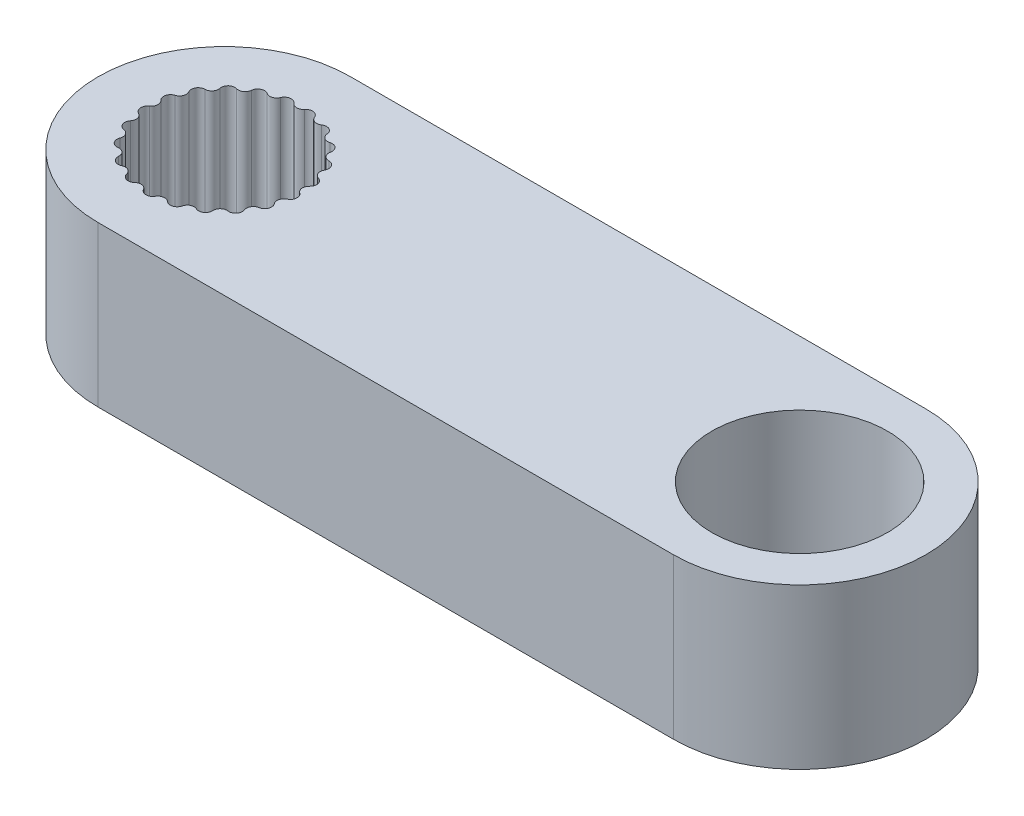
SolidWorks part; units mm, degrees
ref_plane "Front Plane" through (0, 0, 0) normal (0, 0, 1) x (1, 0, 0)
ref_plane "Top Plane" through (0, 0, 0) normal (0, 1, 0) x (1, 0, 0)
ref_plane "Right Plane" through (0, 0, 0) normal (1, 0, 0) x (0, 0, -1)
sketch "Sketch1" plane through (0, 0, 0) normal (0, 1, 0) x (1, 0, 0)
  line L0 (0, 0) -> (0, 4.4464) construction
  line L1 (0, 0) -> (0.6627, 4.3968) construction
  line L2 (0, 0) -> (1.3106, 4.2489) construction
  line L3 (0, 0) -> (1.9292, 4.0061) construction
  line L4 (0, 0) -> (2.5048, 3.6738) construction
  line L5 (0, 0) -> (3.0243, 3.2595) construction
  line L6 (0, 0) -> (3.4764, 2.7723) construction
  line L7 (0, 0) -> (3.8507, 2.2232) construction
  line L8 (0, 0) -> (4.1391, 1.6245) construction
  line L9 (0, 0) -> (4.3349, 0.9894) construction
  line L10 (0, 0) -> (4.434, 0.3323) construction
  line L11 (0, 0) -> (4.434, -0.3323) construction
  line L12 (0, 0) -> (4.3349, -0.9894) construction
  line L13 (0, 0) -> (4.1391, -1.6245) construction
  line L14 (0, 0) -> (3.8507, -2.2232) construction
  line L15 (0, 0) -> (3.4764, -2.7723) construction
  line L16 (0, 0) -> (3.0243, -3.2595) construction
  line L17 (0, 0) -> (2.5048, -3.6738) construction
  line L18 (0, 0) -> (1.9292, -4.0061) construction
  line L19 (0, 0) -> (1.3106, -4.2489) construction
  line L20 (0, 0) -> (0.6627, -4.3968) construction
  line L21 (0, 0) -> (0, -4.4464) construction
  line L22 (0, 0) -> (-0.6627, -4.3968) construction
  line L23 (0, 0) -> (-1.3106, -4.2489) construction
  line L24 (0, 0) -> (-1.9292, -4.0061) construction
  line L25 (0, 0) -> (-2.5048, -3.6738) construction
  line L26 (0, 0) -> (-3.0243, -3.2595) construction
  line L27 (0, 0) -> (-3.4764, -2.7723) construction
  line L28 (0, 0) -> (-3.8507, -2.2232) construction
  line L29 (0, 0) -> (-4.1391, -1.6245) construction
  line L30 (0, 0) -> (-4.3349, -0.9894) construction
  line L31 (0, 0) -> (-4.434, -0.3323) construction
  line L32 (0, 0) -> (-4.434, 0.3323) construction
  line L33 (0, 0) -> (-4.3349, 0.9894) construction
  line L34 (0, 0) -> (-4.1391, 1.6245) construction
  line L35 (0, 0) -> (-3.8507, 2.2232) construction
  line L36 (0, 0) -> (-3.4764, 2.7723) construction
  line L37 (0, 0) -> (-3.0243, 3.2595) construction
  line L38 (0, 0) -> (-2.5048, 3.6738) construction
  line L39 (0, 0) -> (-1.9292, 4.0061) construction
  line L40 (0, 0) -> (-1.3106, 4.2489) construction
  line L41 (0, 0) -> (-0.6627, 4.3968) construction
  circle A1 centre (0, 0) radius 2.45 construction
  circle A5 centre (0, 0) radius 3.95
  circle A14 centre (0, 0) radius 2.2653 construction
  arc A22 (-0.1666, 2.3451) -> (0, 2.2653) centre (0, 2.479) ccw
  arc A23 (-0.1666, 2.3451) -> (-0.532, 2.2901) centre (-0.3333, 2.2113) ccw
  arc A24 (-0.6677, 2.1646) -> (-0.532, 2.2901) centre (-0.7307, 2.3689) ccw
  arc A25 (0, 2.2653) -> (0.1666, 2.3451) centre (0, 2.479) ccw
  arc A26 (0.532, 2.2901) -> (0.1666, 2.3451) centre (0.3333, 2.2113) ccw
  arc A27 (0.532, 2.2901) -> (0.6677, 2.1646) centre (0.7307, 2.3689) ccw
  arc A28 (0.6677, 2.1646) -> (0.8505, 2.1918) centre (0.7307, 2.3689) ccw
  arc A29 (1.1834, 2.0315) -> (0.8505, 2.1918) centre (0.9703, 2.0148) ccw
  arc A30 (1.1834, 2.0315) -> (1.2761, 1.8716) centre (1.3965, 2.0483) ccw
  arc A31 (1.2761, 1.8716) -> (1.4588, 1.8438) centre (1.3965, 2.0483) ccw
  arc A32 (1.7296, 1.5925) -> (1.4588, 1.8438) centre (1.521, 1.6393) ccw
  arc A33 (1.7296, 1.5925) -> (1.7711, 1.4124) centre (1.9382, 1.5456) ccw
  arc A34 (1.7711, 1.4124) -> (1.9374, 1.3319) centre (1.9382, 1.5456) ccw
  arc A35 (2.1221, 1.0119) -> (1.9374, 1.3319) centre (1.9366, 1.1181) ccw
  arc A36 (2.1221, 1.0119) -> (2.1087, 0.8276) centre (2.3077, 0.9057) ccw
  arc A37 (2.1087, 0.8276) -> (2.2439, 0.7016) centre (2.3077, 0.9057) ccw
  arc A38 (2.3261, 0.3414) -> (2.2439, 0.7016) centre (2.1802, 0.4976) ccw
  arc A39 (2.3261, 0.3414) -> (2.2589, 0.1693) centre (2.4721, 0.1853) ccw
  arc A40 (2.2589, 0.1693) -> (2.351, 0.0091) centre (2.4721, 0.1853) ccw
  arc A41 (2.3234, -0.3594) -> (2.351, 0.0091) centre (2.23, -0.1671) ccw
  arc A42 (2.3234, -0.3594) -> (2.2085, -0.5041) centre (2.4169, -0.5516) ccw
  arc A43 (2.2085, -0.5041) -> (2.2493, -0.6843) centre (2.4169, -0.5516) ccw
  arc A44 (2.1143, -1.0283) -> (2.2493, -0.6843) centre (2.0817, -0.817) ccw
  arc A45 (2.1143, -1.0283) -> (1.9618, -1.1326) centre (2.1469, -1.2395) ccw
  arc A46 (1.9618, -1.1326) -> (1.9476, -1.3169) centre (2.1469, -1.2395) ccw
  arc A47 (1.7173, -1.6058) -> (1.9476, -1.3169) centre (1.7484, -1.3943) ccw
  arc A48 (1.7173, -1.6058) -> (1.5408, -1.6606) centre (1.6862, -1.8173) ccw
  arc A49 (1.5408, -1.6606) -> (1.4729, -1.8325) centre (1.6862, -1.8173) ccw
  arc A50 (1.1677, -2.0406) -> (1.4729, -1.8325) centre (1.2597, -1.8477) ccw
  arc A51 (1.1677, -2.0406) -> (0.9829, -2.0409) centre (1.0756, -2.2335) ccw
  arc A52 (0.9829, -2.0409) -> (0.8674, -2.1852) centre (1.0756, -2.2335) ccw
  arc A53 (0.5143, -2.2941) -> (0.8674, -2.1852) centre (0.6591, -2.1369) ccw
  arc A54 (0.5143, -2.2941) -> (0.3376, -2.24) centre (0.3695, -2.4513) ccw
  arc A55 (0.3376, -2.24) -> (0.1847, -2.3438) centre (0.3695, -2.4513) ccw
  arc A56 (-0.1847, -2.3438) -> (0.1847, -2.3438) centre (0, -2.2362) ccw
  arc A57 (-0.1847, -2.3438) -> (-0.3376, -2.24) centre (-0.3695, -2.4513) ccw
  arc A58 (-0.3376, -2.24) -> (-0.5143, -2.2941) centre (-0.3695, -2.4513) ccw
  arc A59 (-0.8674, -2.1852) -> (-0.5143, -2.2941) centre (-0.6591, -2.1369) ccw
  arc A60 (-0.8674, -2.1852) -> (-0.9829, -2.0409) centre (-1.0756, -2.2335) ccw
  arc A61 (-0.9829, -2.0409) -> (-1.1677, -2.0406) centre (-1.0756, -2.2335) ccw
  arc A62 (-1.4729, -1.8325) -> (-1.1677, -2.0406) centre (-1.2597, -1.8477) ccw
  arc A63 (-1.4729, -1.8325) -> (-1.5408, -1.6606) centre (-1.6862, -1.8173) ccw
  arc A64 (-1.5408, -1.6606) -> (-1.7173, -1.6058) centre (-1.6862, -1.8173) ccw
  arc A65 (-1.9476, -1.3169) -> (-1.7173, -1.6058) centre (-1.7484, -1.3943) ccw
  arc A66 (-1.9476, -1.3169) -> (-1.9618, -1.1326) centre (-2.1469, -1.2395) ccw
  arc A67 (-1.9618, -1.1326) -> (-2.1143, -1.0283) centre (-2.1469, -1.2395) ccw
  arc A68 (-2.2493, -0.6843) -> (-2.1143, -1.0283) centre (-2.0817, -0.817) ccw
  arc A69 (-2.2493, -0.6843) -> (-2.2085, -0.5041) centre (-2.4169, -0.5516) ccw
  arc A70 (-2.2085, -0.5041) -> (-2.3234, -0.3594) centre (-2.4169, -0.5516) ccw
  arc A71 (-2.351, 0.0091) -> (-2.3234, -0.3594) centre (-2.23, -0.1671) ccw
  arc A72 (-2.351, 0.0091) -> (-2.2589, 0.1693) centre (-2.4721, 0.1853) ccw
  arc A73 (-2.2589, 0.1693) -> (-2.3261, 0.3414) centre (-2.4721, 0.1853) ccw
  arc A74 (-2.2439, 0.7016) -> (-2.3261, 0.3414) centre (-2.1802, 0.4976) ccw
  arc A75 (-2.2439, 0.7016) -> (-2.1087, 0.8276) centre (-2.3077, 0.9057) ccw
  arc A76 (-2.1087, 0.8276) -> (-2.1221, 1.0119) centre (-2.3077, 0.9057) ccw
  arc A77 (-1.9374, 1.3319) -> (-2.1221, 1.0119) centre (-1.9366, 1.1181) ccw
  arc A78 (-1.9374, 1.3319) -> (-1.7711, 1.4124) centre (-1.9382, 1.5456) ccw
  arc A79 (-1.7711, 1.4124) -> (-1.7296, 1.5925) centre (-1.9382, 1.5456) ccw
  arc A80 (-1.4588, 1.8438) -> (-1.7296, 1.5925) centre (-1.521, 1.6393) ccw
  arc A81 (-1.4588, 1.8438) -> (-1.2761, 1.8716) centre (-1.3965, 2.0483) ccw
  arc A82 (-1.2761, 1.8716) -> (-1.1834, 2.0315) centre (-1.3965, 2.0483) ccw
  arc A83 (-0.8505, 2.1918) -> (-1.1834, 2.0315) centre (-0.9703, 2.0148) ccw
  arc A84 (-0.8505, 2.1918) -> (-0.6677, 2.1646) centre (-0.7307, 2.3689) ccw
  point P27 (0, 0)
  point P50 (0, 0)
  point P198 (0, 0)
  dimension "D1" = 1.5
  dimension "D2" = 4.9
  dimension "D3" = 42
  dimension "D4" = 2.2362
  dimension "D5" = 4.5305
  dimension "D6" = 4.5305
  dimension "D7" = 21
extrude "Boss-Extrude1" add sketch "Sketch1" along normal blind 5
sketch "Sketch2" plane through (0, 0, 0) normal (0, -1, 0) x (1, 0, 0)
  line L0 (0, 3.95) -> (18, 3.95)
  line L1 (0, -3.95) -> (18, -3.95)
  circle A0 centre (0, 0) radius 3.95 construction
  arc A1 (18, -3.95) -> (18, 3.95) centre (18, 0) ccw
  arc A2 (0, -3.95) -> (0, 3.95) centre (0, 0) ccw
  dimension "D1" = 18
extrude "Boss-Extrude2" add sketch "Sketch2" against normal up to surface (5 mm away) up to face at (0, 5, 3.95)
sketch "Sketch3" plane through (0, 5, 0) normal (0, 1, 0) x (1, 0, 0)
  circle A0 centre (18, 0) radius 2.75
  dimension "D1" = 5.5
extrude "Cut-Extrude1" cut sketch "Sketch3" against normal up to surface (5 mm away) up to face at (9, 0, 0)
equation "\"r0.247\"=0.713093"
